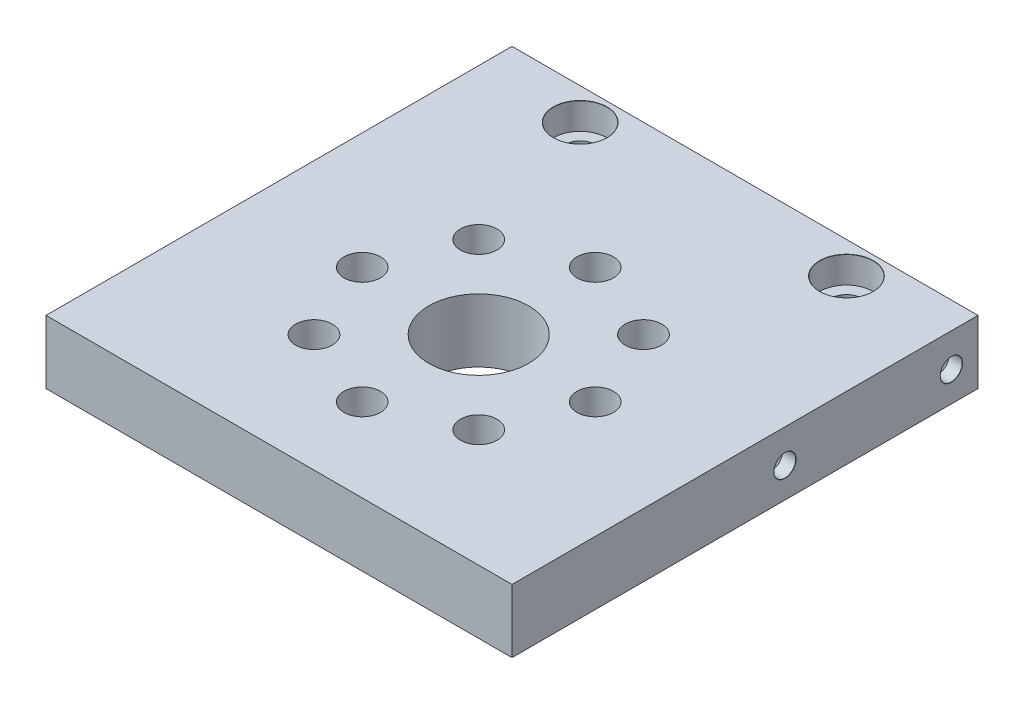
SolidWorks part; units mm, degrees
material "1060 Alloy"
ref_plane "Front Plane" through (0, 0, 0) normal (0, 0, 1) x (1, 0, 0)
ref_plane "Top Plane" through (0, 0, 0) normal (0, 1, 0) x (1, 0, 0)
ref_plane "Right Plane" through (0, 0, 0) normal (1, 0, 0) x (0, 0, -1)
sketch "Sketch1" plane through (0, 0, 0) normal (0, 1, 0) x (1, 0, 0)
  line L1 (-35, -35) -> (35, -35)
  line L2 (-35, -35) -> (-35, 35)
  line L3 (-35, 35) -> (35, 35)
  line L4 (35, -35) -> (35, 35)
  line L5 (-35, -35) -> (35, 35) construction
  line L6 (-35, 35) -> (35, -35) construction
  point P0 (0, 0)
  dimension "D1" = 70
  dimension "D2" = 70
extrude "Boss-Extrude1" add sketch "Sketch1" along normal blind 9.525
sketch "Sketch2" plane through (0, 0, 0) normal (0, -1, 0) x (1, 0, 0)
  line L1 (-35, 35) -> (35, 35) construction
  line L2 (-35, -35) -> (-35, 35) construction
  circle A0 centre (0, 5) radius 17.5 construction
  point P4 (0, 22.5)
  point P6 (12.3744, 17.3744)
  point P7 (17.5, 5)
  point P8 (12.3744, -7.3744)
  point P9 (0, -12.5)
  point P10 (-12.3744, -7.3744)
  point P11 (-17.5, 5)
  point P12 (-12.3744, 17.3744)
  point P13 (0, 5)
  dimension "D2" = 35
  dimension "D3" = 30
  dimension "D4" = 35
  dimension "D1" = 8
hole_wizard "CBORE for M5 SHCS2" positions "Sketch3" profile "Sketch4" counterbore size "M5" standard "ANSI Metric" end condition through all
sketch "Sketch3" plane through (0, 0, 0) normal (0, -1, 0) x (-1, 0, 0)
  point P0 (0, -22.5)
  point P3 (-12.3744, -17.3744)
  point P6 (-17.5, -5)
  point P9 (-12.3744, 7.3744)
  point P12 (0, 12.5)
  point P15 (12.3744, 7.3744)
  point P18 (17.5, -5)
  point P21 (12.3744, -17.3744)
sketch "Sketch4" plane through (0, 0, 22.5) normal (1, 0, 0) x (0, 0, -1)
  line L0 (0, 0) -> (0, 9.525)
  line L1 (0, 9.525) -> (2.75, 9.525)
  line L3 (2.75, 9.525) -> (2.75, 5)
  line L4 (5, 5) -> (2.75, 5)
  line L5 (5, 5) -> (5, 0.025)
  line L6 (5, 0.025) -> (5.025, 0)
  line L7 (5.025, 0) -> (0, 0)
  line L8 (-5, 0.025) -> (-5.025, 0) construction
  line L11 (0, -6.35) -> (0, 107.95) construction
  dimension "Thru Hole Dia." = 5.5
  dimension "Thru Hole Depth" = 9.525
  dimension "C'Bore Dia." = 10
  dimension "C'Bore Depth" = 5
  dimension "Near C'Sink Dia." = 10.05
  dimension "Near C'Sink Angle" = 90
sketch "Sketch5" plane through (35, 0, 0) normal (1, 0, 0) x (0, 0, -1)
  line L0 (35, 4.5) -> (-35, 4.5) construction
  line L1 (35, 9.525) -> (35, 0) construction
  line L3 (-35, 0) -> (35, 0) construction
  point P6 (31, 4.5)
  point P7 (6, 4.5)
  point P8 (0, 0)
  point P9 (0, 0)
  point P10 (0, 0)
  dimension "D1" = 4
  dimension "D2" = 25
  dimension "D3" = 4.5
hole_wizard "Tap Drill for M4x0.7 Tap1" positions "Sketch6" profile "Sketch8" hole size "M4x0.7" standard "ANSI Metric"
sketch "Sketch6" plane through (35, 0, 0) normal (1, 0, 0) x (0, 0, -1)
  point P0 (6, 4.5)
  point P3 (31, 4.5)
sketch "Sketch8" plane through (35, 4.5, -6) normal (0, 1, 0) x (0, 0, -1)
  line L0 (0, 0) -> (0, 2.9914)
  line L1 (0, 2.9914) -> (1.65, 2)
  line L2 (1.65, 2) -> (1.65, 0.025)
  line L3 (1.65, 0.025) -> (1.675, 0)
  line L5 (1.675, 0) -> (0, 0)
  line L6 (-1.65, 0.025) -> (-1.675, 0) construction
  line L10 (0, 2.9914) -> (-1.65, 2) construction
  line L11 (0, -6.35) -> (0, 107.95) construction
  dimension "Hole Dia." = 3.3
  dimension "Hole Depth" = 2
  dimension "Near C'Sink Dia." = 3.35
  dimension "Near C'Sink Angle" = 90
  dimension "Drill Angle" = 118
sketch "Sketch9" plane through (0, 0, 0) normal (0, -1, 0) x (1, 0, 0)
  circle A0 centre (0, 5) radius 7.5
  circle A1 centre (0, 5) radius 17.5 construction
  dimension "D1" = 15
extrude "Cut-Extrude1" cut sketch "Sketch9" against normal through all
sketch "Sketch10" plane through (0, 9.525, 0) normal (0, -1, 0) x (1, 0, 0)
  line L0 (35, -30.2375) -> (-35, -30.2375) construction
  line L1 (35, 35) -> (35, -35) construction
  line L2 (-35, -35) -> (-35, 35) construction
  line L3 (35, -35) -> (-35, -35) construction
  line L4 (0, -5.2388) -> (0, 5.2388) construction
  point P8 (20, -30.2375)
  point P11 (-20, -30.2375)
  dimension "D1" = 4.7625
  dimension "D2" = 15
hole_wizard "CBORE for M4 SHCS1" positions "Sketch14" profile "Sketch15" counterbore size "M4" standard "ANSI Metric" end condition through all
sketch "Sketch14" plane through (0, 9.525, 0) normal (0, 1, 0) x (1, 0, 0)
  point P0 (-20, 30.2375)
  point P3 (20, 30.2375)
sketch "Sketch15" plane through (-20, 9.525, -30.2375) normal (1, 0, 0) x (0, 0, 1)
  line L0 (0, 0) -> (0, 9.525)
  line L1 (0, 9.525) -> (2.25, 9.525)
  line L3 (2.25, 9.525) -> (2.25, 4)
  line L4 (4, 4) -> (2.25, 4)
  line L5 (4, 4) -> (4, 0.025)
  line L6 (4, 0.025) -> (4.025, 0)
  line L7 (4.025, 0) -> (0, 0)
  line L8 (-4, 0.025) -> (-4.025, 0) construction
  line L11 (0, -6.35) -> (0, 107.95) construction
  dimension "Thru Hole Dia." = 4.5
  dimension "Thru Hole Depth" = 9.525
  dimension "C'Bore Dia." = 8
  dimension "C'Bore Depth" = 4
  dimension "Near C'Sink Dia." = 8.05
  dimension "Near C'Sink Angle" = 90
mirror "Mirror1" about plane through (0, 0, 0) normal (1, 0, 0) of "Tap Drill for M4x0.7 Tap1"
